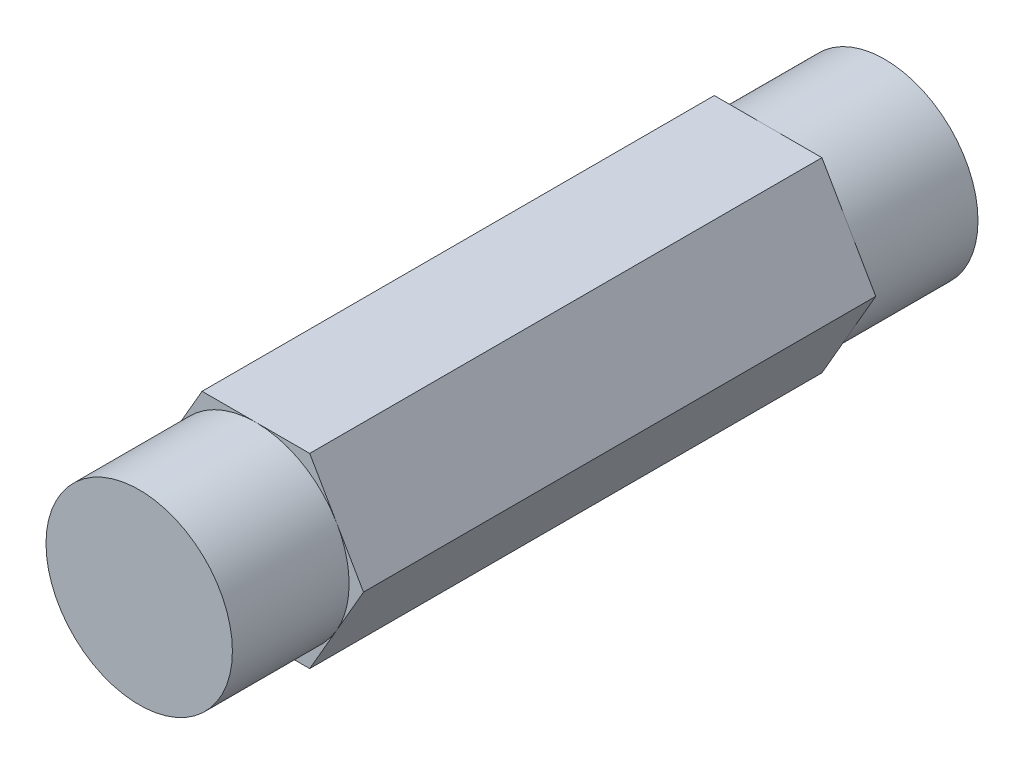
SolidWorks part; units mm, degrees
ref_plane "Front Plane" through (0, 0, 0) normal (0, 0, 1) x (1, 0, 0)
ref_plane "Top Plane" through (0, 0, 0) normal (0, 1, 0) x (1, 0, 0)
ref_plane "Right Plane" through (0, 0, 0) normal (1, 0, 0) x (0, 0, -1)
sketch "Sketch1" plane through (0, 0, 0) normal (0, 0, 1) x (1, 0, 0)
  line L1 (7.3323, 0) -> (3.6662, 6.35)
  line L2 (3.6662, 6.35) -> (-3.6662, 6.35)
  line L3 (-3.6662, 6.35) -> (-7.3323, 0)
  line L4 (-7.3323, 0) -> (-3.6662, -6.35)
  line L5 (-3.6662, -6.35) -> (3.6662, -6.35)
  line L6 (3.6662, -6.35) -> (7.3323, 0)
  circle A0 centre (0, 0) radius 6.35 construction
  dimension "D1" = 12.7
extrude "Boss-Extrude1" add sketch "Sketch1" along normal mid plane 50.8
sketch "Sketch3" plane through (0, 0, 25.4) normal (0, 0, 1) x (1, 0, 0)
  circle A0 centre (0, 0) radius 6.35
extrude "Cut-Extrude2" cut sketch "Sketch3" against normal blind 7.9502 flip side to cut
mirror "Mirror1" about plane through (0, 0, 0) normal (0, 0, 1) of "Cut-Extrude2"
